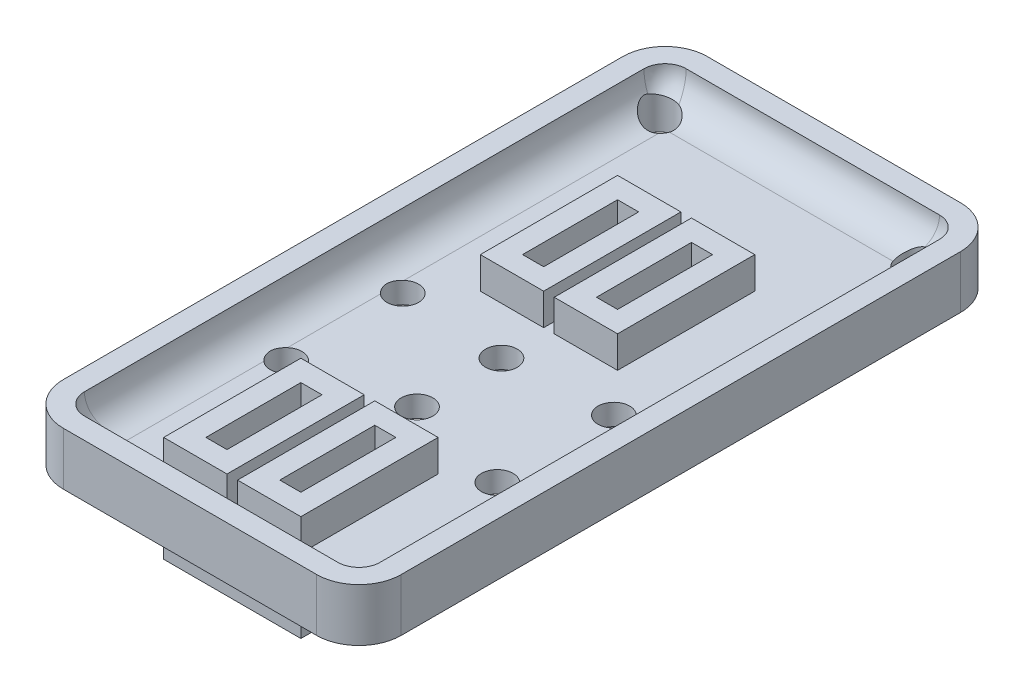
SolidWorks part; units mm, degrees
ref_plane "Front Plane" through (0, 0, 0) normal (0, 0, 1) x (1, 0, 0)
ref_plane "Top Plane" through (0, 0, 0) normal (0, 1, 0) x (1, 0, 0)
ref_plane "Right Plane" through (0, 0, 0) normal (1, 0, 0) x (0, 0, -1)
sketch "Sketch1" plane through (0, 25, 0) normal (0, 1, 0) x (1, 0, 0)
  line L0 (4.5, 17) -> (2.5, 17)
  line L2 (-16, -28) -> (16, -28)
  line L3 (-16, -28) -> (-16, 33)
  line L4 (-16, 33) -> (16, 33)
  line L5 (16, -28) -> (16, 33)
  line L15 (4.5, -13) -> (2.5, -13)
  line L16 (2.5, -13) -> (2.5, -22)
  line L17 (2.5, -22) -> (4.5, -22)
  line L18 (-4.5, -22) -> (-2.5, -22)
  line L19 (-4.5, -13) -> (-4.5, -22)
  line L20 (-2.5, -22) -> (-2.5, -13)
  line L21 (-2.5, -13) -> (-4.5, -13)
  line L23 (4.5, -22) -> (4.5, -13)
  line L24 (2.5, 17) -> (2.5, 8)
  line L25 (2.5, 8) -> (4.5, 8)
  line L26 (4.5, 8) -> (4.5, 17)
  line L27 (-4.5, 8) -> (-2.5, 8)
  line L28 (-2.5, 8) -> (-2.5, 17)
  line L29 (-2.5, 17) -> (-4.5, 17)
  line L30 (-4.5, 17) -> (-4.5, 8)
  point P0 (-4.5, -12.9049)
  point P6 (0, 33)
  dimension "D2" = 30
  dimension "D3" = 32
  dimension "D4" = 61
  dimension "D5" = 28
  dimension "D6" = 2
  dimension "D7" = 9
  dimension "D8" = 7
  dimension "D9" = 4.5
  dimension "D10" = 13
  dimension "D1" = 2
extrude "Boss-Extrude1" add sketch "Sketch1" along normal blind 5
fillet "Fillet1" radius 4 4 edges at (-16, 27.5, -33) (16, 27.5, -33) (16, 27.5, 28) (-16, 27.5, 28)
sketch "Sketch3" plane through (0, 25, 0) normal (0, -1, 0) x (1, 0, 0)
  line L0 (-6.5, 11) -> (6.5, 11)
  line L1 (6.5, 11) -> (6.5, 24)
  line L2 (6.5, 24) -> (-6.5, 24)
  line L3 (-6.5, 24) -> (-6.5, 11)
  line L4 (2.5, 22) -> (4.5, 22) construction
  line L5 (-4.5, 13) -> (-4.5, 22) construction
  line L6 (4.5, 22) -> (4.5, 13) construction
  line L8 (4.5, 13) -> (4.5, 22)
  line L9 (4.5, 22) -> (-4.5, 22)
  line L10 (-4.5, 22) -> (-4.5, 13)
  line L11 (-4.5, 13) -> (4.5, 13)
  line L16 (-6.5, -19) -> (6.5, -19)
  line L17 (6.5, -19) -> (6.5, -6)
  line L18 (6.5, -6) -> (-6.5, -6)
  line L19 (-6.5, -6) -> (-6.5, -19)
  line L20 (4.5, -17) -> (4.5, -8)
  line L21 (4.5, -8) -> (-4.5, -8)
  line L22 (-4.5, -8) -> (-4.5, -17)
  line L23 (-4.5, -17) -> (4.5, -17)
  line L25 (4.5, 13) -> (2.5, 13) construction
  point P18 (-5.1883, 22)
  point P23 (4.5, 12.1127)
  dimension "D4" = 30
  dimension "D2" = 2
  dimension "D3" = 2
extrude "Boss-Extrude3" add sketch "Sketch3" along normal blind 5
shell "Shell1" thickness 2 removed face at (-3.5, 30, 17.5)
fillet "Fillet2" radius 3 8 edges at (13.4142, 27, -30.4142) (14, 27, -2.5) (13.4142, 27, 25.4142) (0, 27, 26) (-13.4142, 27, 25.4142) (-14, 27, -2.5) (-13.4142, 27, -30.4142) (0, 27, -31)
sketch "Sketch7" plane through (0, 25, 0) normal (0, -1, 0) x (1, 0, 0)
  line L0 (12, -33) -> (-12, -33) construction
  line L1 (-16, -29) -> (-16, 24) construction
  line L2 (16, 24) -> (16, -29) construction
  line L4 (0, -23.1) -> (0, 23.1) construction
  circle A17 centre (-12, -28.5) radius 1.5
  circle A18 centre (10, -2.15) radius 1.5
  circle A20 centre (12, -28.5) radius 1.5
  circle A21 centre (-10, 8.8957) radius 1.5
  circle A22 centre (-10, 8.8957) radius 1.5
  circle A23 centre (-10, -2.15) radius 1.5
  circle A24 centre (-10, -2.15) radius 1.5
  circle A25 centre (10, 8.8957) radius 1.5
  circle A27 centre (0, 6.5) radius 1.5
  circle A28 centre (0, -1.5) radius 1.5
  point P19 (0, 0)
  point P20 (0, -1.3299)
  point P21 (0, 0)
  point P25 (0, 0)
  point P28 (0, 0)
  point P30 (11.5203, -29.7106)
  dimension "D5" = 3
  dimension "D1" = 3
  dimension "D6" = 8
  dimension "D7" = 4.5
  dimension "D8" = 4
  dimension "D2" = 4.5
  dimension "D9" = 4
  dimension "D3" = 0.5
  dimension "D4" = 0.5
extrude "Cut-Extrude1" cut sketch "Sketch7" against normal through all
